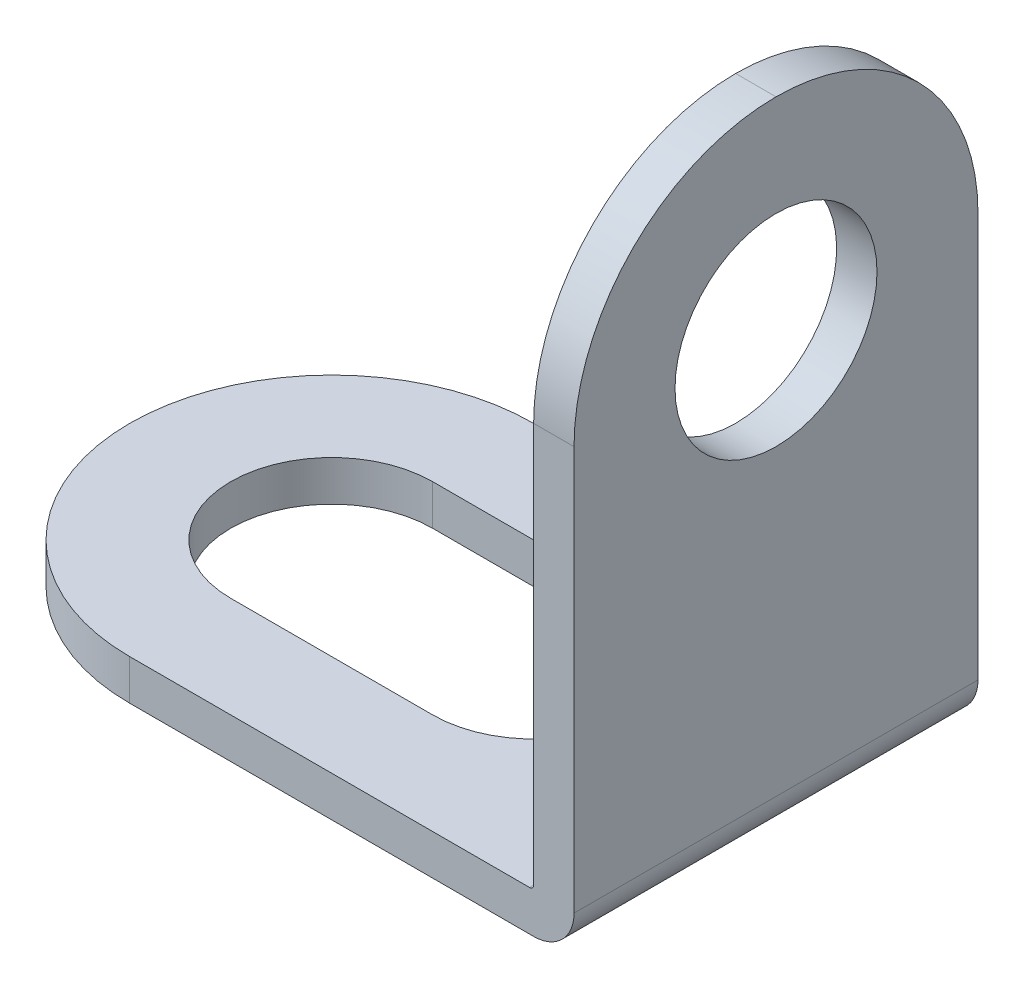
SolidWorks part; units mm, degrees
material "1.4000 (X6Cr13)"
ref_plane "Ebene vorne" through (0, 0, 0) normal (0, 0, 1) x (1, 0, 0)
ref_plane "Ebene oben" through (0, 0, 0) normal (0, 1, 0) x (1, 0, 0)
ref_plane "Ebene rechts" through (0, 0, 0) normal (1, 0, 0) x (0, 0, -1)
sketch "Skizze1" plane through (0, 0, 0) normal (0, 0, 1) x (1, 0, 0)
  line L0 (0, 15) -> (0, 0)
  line L1 (0, 0) -> (-15, 0)
  dimension "D1" = 15
extrude "Linear-Austragen-Dünn1" add sketch "Skizze1" along normal mid plane 10 thin thin type one direction reverse wall 1
fillet "Verrundung1" radius 5 4 edges at (-15, -0.5, -5) (-15, -0.5, 5) (0.5, 15, -5) (0.5, 15, 5)
fillet "Verrundung2" radius 1 1 edges at (1, -1, 0)
fillet "Verrundung3" radius 0.1 1 edges at (0, 0, 0)
sketch "Skizze2" plane through (0, 0, 0) normal (-1, 0, 0) x (0, 0, 1)
  circle A0 centre (0, 10) radius 2.5
  arc A1 (5, 10) -> (0, 15) centre (0, 10) ccw construction
  dimension "D1" = 5
extrude "Schnitt-Linear austragen1" cut sketch "Skizze2" against normal blind 10
sketch "Skizze3" plane through (0, 0, 0) normal (0, 1, 0) x (1, 0, 0)
  line L0 (-10, 0) -> (-5, 0) construction
  line L1 (-10, 2.5) -> (-5, 2.5)
  line L2 (-10, -2.5) -> (-5, -2.5)
  arc A0 (-10, 2.5) -> (-10, -2.5) centre (-10, 0) ccw
  arc A1 (-5, -2.5) -> (-5, 2.5) centre (-5, 0) ccw
  arc A2 (-10, 5) -> (-15, 0) centre (-10, 0) ccw construction
  point P3 (-7.5, 0)
  dimension "D1" = 5
  dimension "D2" = 5
extrude "Schnitt-Linear austragen2" cut sketch "Skizze3" against normal blind 10
